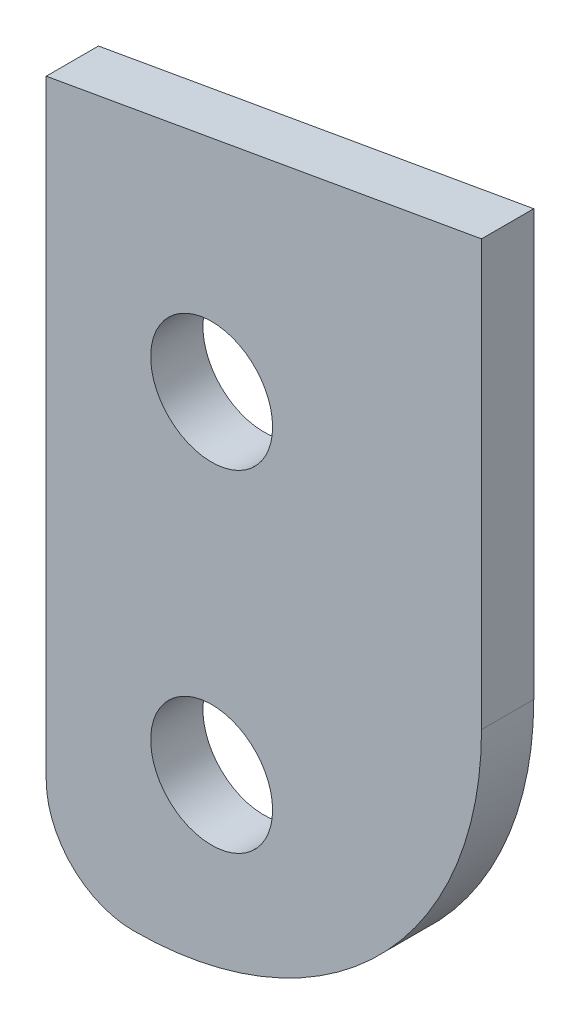
SolidWorks part; units mm, degrees
material "AISI 304"
ref_plane "Спереди" through (0, 0, 0) normal (0, 0, 1) x (1, 0, 0)
ref_plane "Сверху" through (0, 0, 0) normal (0, 1, 0) x (1, 0, 0)
ref_plane "Справа" through (0, 0, 0) normal (1, 0, 0) x (0, 0, -1)
sketch "Эскиз1" plane through (0, 0, 0) normal (0, 0, 1) x (1, 0, 0)
  line L0 (0, 0) -> (0, 80)
  line L2 (0, 80) -> (50, 88.8163)
  line L3 (0, 0) -> (50, 0)
  line L5 (50, 0) -> (50, 88.8163)
  dimension "D1" = 80
  dimension "D2" = 100
  dimension "D3" = 50
extrude "Бобышка-Вытянуть1" add sketch "Эскиз1" along normal blind 6
sketch "Эскиз2" plane through (0, 0, 0) normal (0, 0, 1) x (1, 0, 0)
  line L0 (19, 20) -> (19, 58.1) construction
  line L1 (5, 0) -> (5, 45) construction
  line L2 (5, 45) -> (50, 45) construction
  line L3 (0, 80) -> (0, 0) construction
  line L7 (50, 0) -> (50, 88.8163) construction
  line L8 (50, 50) -> (0, 50) construction
  line L10 (0, 80) -> (0, 0) construction
  line L11 (0, 0) -> (50, 0) construction
  line L13 (0, 0) -> (50, 0) construction
  line L15 (50, 0) -> (50, 88.8163) construction
  circle A2 centre (19, 58.1) radius 7
  circle A3 centre (19, 20) radius 7
  dimension "D1" = 38.1
  dimension "D3" = 14
  dimension "D4" = 19
  dimension "D5" = 50
  dimension "D6" = 20
  dimension "D7" = 5
  dimension "D8" = 5
extrude "Вырез-Вытянуть1" cut sketch "Эскиз2" along normal through all
fillet "Скругление2" radius 40 1 edges at (50, 0, 3)
fillet "Скругление3" radius 10 1 edges at (0, 0, 3)
